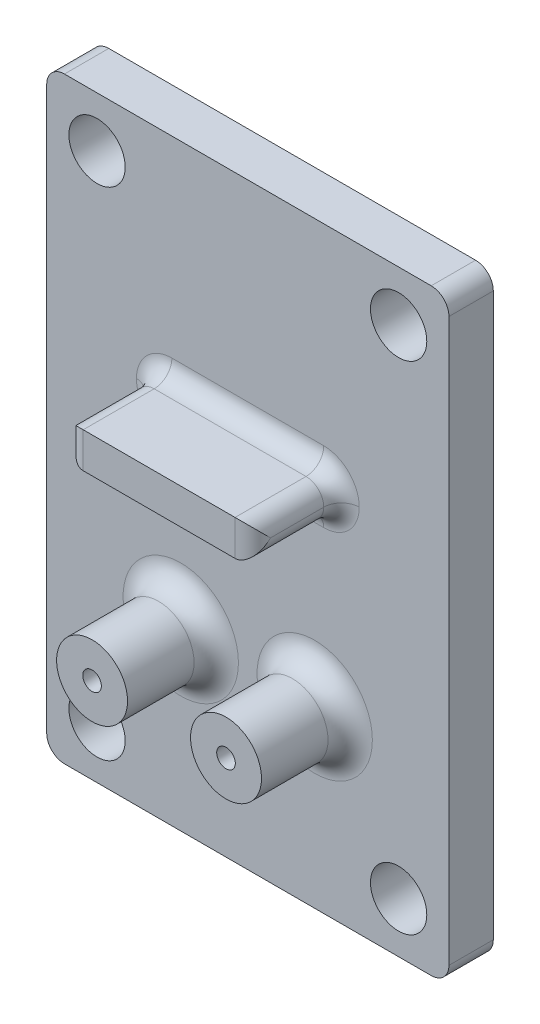
SolidWorks part; units mm, degrees
ref_plane "Front Plane" through (0, 0, 0) normal (0, 0, 1) x (1, 0, 0)
ref_plane "Top Plane" through (0, 0, 0) normal (0, 1, 0) x (1, 0, 0)
ref_plane "Right Plane" through (0, 0, 0) normal (1, 0, 0) x (0, 0, -1)
sketch "Sketch1" plane through (0, 0, 0) normal (0, 0, 1) x (1, 0, 0)
  line L1 (10.56, -17) -> (10.56, 17) construction
  line L2 (10.56, -17) -> (-10.56, -17) construction
  line L3 (-10.56, -17) -> (-10.56, 17) construction
  line L4 (10.56, 17) -> (-10.56, 17) construction
  line L5 (-10.56, 0) -> (10.56, 0) construction
  line L6 (0, -17) -> (0, 17) construction
  line L7 (14, -25) -> (14, 25) construction
  line L8 (14, -25) -> (-14, -25) construction
  line L9 (-14, -25) -> (-14, 25) construction
  line L10 (14, 25) -> (-14, 25) construction
  line L11 (-14, 0) -> (14, 0) construction
  line L12 (0, -25) -> (0, 25) construction
  line L15 (14, -25) -> (14, 25)
  line L21 (-17, 28) -> (17, 28) construction
  line L22 (-17, 28) -> (-17, -28) construction
  line L23 (-17, -28) -> (17, -28) construction
  line L36 (17, 28) -> (17, -28) construction
  line L44 (-22.675, 33.675) -> (22.675, 33.675)
  line L45 (-22.675, 33.675) -> (-22.675, -33.675)
  line L46 (-22.675, -33.675) -> (22.675, -33.675)
  line L47 (22.675, 33.675) -> (22.675, -33.675)
  line L58 (98, -25) -> (98, 25)
  line L59 (98, 25) -> (70, 25)
  line L60 (70, -25) -> (70, 25)
  line L61 (98, -25) -> (70, -25)
  line L62 (94.56, -17) -> (94.56, 17) construction
  line L63 (94.56, -17) -> (73.44, -17) construction
  line L64 (73.44, -17) -> (73.44, 17) construction
  line L65 (94.56, 17) -> (73.44, 17) construction
  line L66 (73.44, 0) -> (94.56, 0) construction
  line L67 (84, -17) -> (84, 17) construction
  line L68 (84, -25) -> (84, 25) construction
  line L69 (70, -25) -> (70, 25)
  line L70 (66.56, -17) -> (66.56, 17) construction
  line L71 (56, -17) -> (56, 17) construction
  line L72 (56, -25) -> (56, 25) construction
  line L73 (70, 0) -> (98, 0) construction
  line L74 (42, -25) -> (42, 25)
  line L75 (70, -25) -> (42, -25)
  line L76 (42, -25) -> (42, 25)
  line L77 (70, 25) -> (42, 25)
  line L78 (38.56, -17) -> (38.56, 17) construction
  line L79 (28, -17) -> (28, 17) construction
  line L80 (28, -25) -> (28, 25) construction
  line L81 (66.56, -17) -> (45.44, -17) construction
  line L82 (45.44, -17) -> (45.44, 17) construction
  line L83 (66.56, 17) -> (45.44, 17) construction
  line L84 (45.44, 0) -> (66.56, 0) construction
  line L85 (42, 0) -> (70, 0) construction
  line L86 (42, -25) -> (14, -25)
  line L87 (42, 25) -> (14, 25)
  line L88 (38.56, -17) -> (17.44, -17) construction
  line L89 (38.56, 17) -> (17.44, 17) construction
  line L90 (17.44, 0) -> (38.56, 0) construction
  line L91 (14, 0) -> (42, 0) construction
  line L92 (17.44, -17) -> (17.44, 17) construction
  circle A0 centre (7.54, -14) radius 1.5 construction
  circle A1 centre (-7.56, -14) radius 1.5 construction
  circle A8 centre (91.54, -14) radius 1.5 construction
  circle A9 centre (76.44, -14) radius 1.5 construction
  circle A10 centre (63.54, -14) radius 1.5 construction
  circle A11 centre (35.54, -14) radius 1.5 construction
  circle A12 centre (48.44, -14) radius 1.5 construction
  circle A13 centre (20.44, -14) radius 1.5 construction
  circle A15 centre (-17, 28) radius 3.175
  circle A16 centre (17, 28) radius 3.175
  circle A17 centre (17, -28) radius 3.175
  circle A18 centre (-17, -28) radius 3.175
  point P0 (0, 0)
  point P4 (0, 0)
  point P10 (6.04, -14)
  point P11 (7.54, -12.5)
  point P12 (-9.06, -14)
  point P13 (-7.56, -12.5)
  point P14 (7.54, -12.5)
  point P17 (-7.56, -12.5)
  point P19 (20.44, -12.5)
  point P20 (20.44, -12.5)
  point P21 (-6.06, -14)
  point P22 (18.94, -14)
  point P23 (28, 0)
  point P29 (28, 0)
  point P30 (34.04, -14)
  point P33 (35.54, -12.5)
  point P38 (48.44, -12.5)
  point P39 (17, 0)
  point P40 (48.44, -12.5)
  point P41 (0, 28)
  point P43 (46.94, -14)
  point P45 (35.54, -12.5)
  point P48 (0, -33.675)
  point P49 (-20.175, 28)
  point P50 (15, 27.8346)
  point P51 (56, 0)
  point P52 (-17, 31.175)
  point P56 (22.675, 0)
  point P57 (56, 0)
  point P58 (62.04, -14)
  point P61 (63.54, -12.5)
  point P66 (63.54, -12.5)
  point P76 (76.44, -12.5)
  point P77 (91.54, -12.5)
  point P78 (76.44, -12.5)
  point P79 (84, 0)
  point P80 (74.94, -14)
  point P81 (91.54, -12.5)
  point P82 (90.04, -14)
  point P85 (84, 0)
  dimension "D4" = 3
  dimension "D15" = 2.5
  dimension "D11" = 6.35
  dimension "D1" = 34
  dimension "D2" = 21.12
  dimension "D3" = 8
  dimension "D5" = 3
  dimension "D6" = 3
  dimension "D7" = 3
  dimension "D8" = 12.1
  dimension "D9" = 28
  dimension "D12" = 3
  dimension "D13" = 3
  dimension "D14" = 2.5
  dimension "D10" = 4
extrude "Boss-Extrude1" add sketch "Sketch1" along normal blind 5
sketch "Sketch2" plane through (0, 0, 5) normal (0, 0, 1) x (1, 0, 0)
  line L0 (0, -17) -> (0, 17) construction
  line L1 (-10.56, 6) -> (10.56, 6)
  line L2 (-10.56, 6) -> (-10.56, 10)
  line L3 (-10.56, 10) -> (10.56, 10)
  line L4 (10.56, 6) -> (10.56, 10)
  line L5 (0, 10) -> (0, 6) construction
  line L6 (-10.56, 8) -> (10.56, 8) construction
  line L7 (10.56, -17) -> (10.56, 17) construction
  circle A4 centre (-7.56, -14) radius 4
  circle A5 centre (7.54, -14) radius 4
  circle A16 centre (-7.56, -14) radius 1.05
  circle A17 centre (7.54, -14) radius 1.05
  point P48 (0, 8)
  dimension "D1" = 8
  dimension "D2" = 2.1
  dimension "D3" = 6
  dimension "D5" = 4
extrude "Boss-Extrude2" add sketch "Sketch2" along normal blind 10 contours A5 A17 | A4 A16 | L1 L4 L3 L2
fillet "Fillet1" radius 2 4 edges at (-22.675, 33.675, 2.5) (22.675, 33.675, 2.5) (22.675, -33.675, 2.5) (-22.675, -33.675, 2.5)
fillet "Fillet2" radius 2 8 edges at (0, 10, 5) (0, 6, 5) (10.56, 6, 10) (10.56, 8, 15) (10.56, 10, 10) (-10.56, 10, 10) (-10.56, 8, 15) (-10.56, 6, 10)
fillet "Fillet3" radius 2.5 2 edges at (11.54, -14, 5) (-3.56, -14, 5)
